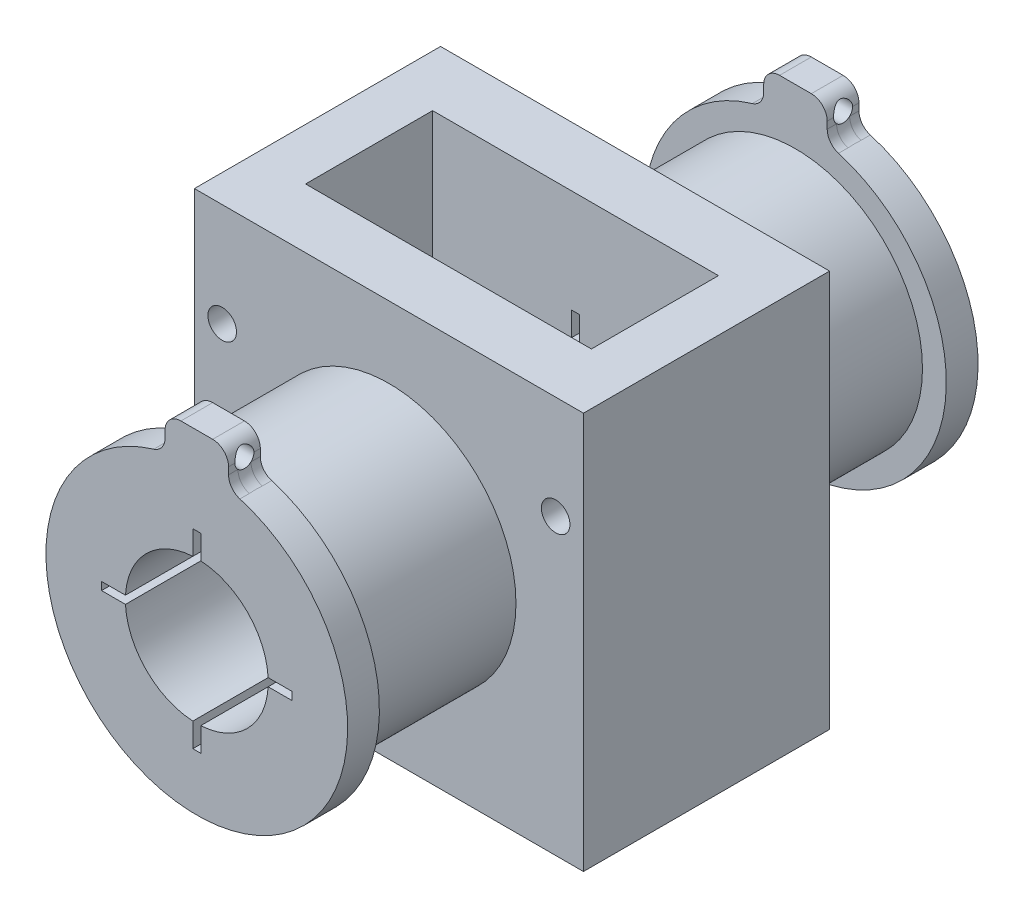
SolidWorks part; units mm, degrees
ref_plane "Front Plane" through (0, 0, 0) normal (0, 0, 1) x (1, 0, 0)
ref_plane "Top Plane" through (0, 0, 0) normal (0, 1, 0) x (1, 0, 0)
ref_plane "Right Plane" through (0, 0, 0) normal (1, 0, 0) x (0, 0, -1)
sketch "Sketch1" plane through (0, 0, 0) normal (0, 0, 1) x (1, 0, 0)
  line L1 (12.25, -12.5) -> (-12.25, -12.5)
  line L2 (12.25, -12.5) -> (12.25, 12.5)
  line L3 (12.25, 12.5) -> (-12.25, 12.5)
  line L4 (-12.25, -12.5) -> (-12.25, 12.5)
  line L5 (12.25, -12.5) -> (-12.25, 12.5) construction
  line L6 (12.25, 12.5) -> (-12.25, -12.5) construction
  point P0 (0, 0)
  dimension "D1" = 24.5
  dimension "D2" = 25
extrude "Boss-Extrude1" add sketch "Sketch1" along normal mid plane 15.5
ref_plane "Plane1" through (0, 0, 7.75) normal (0, 0, 1) x (1, 0, 0)
sketch "Sketch2" plane through (0, 0, 7.75) normal (0, 0, 1) x (1, 0, 0)
  circle A0 centre (0, 0) radius 8
  dimension "D1" = 16
extrude "Boss-Extrude2" add sketch "Sketch2" along normal blind 12.1
mirror "Mirror1" about plane through (0, 0, 0) normal (0, 0, 1) of "Boss-Extrude2"
ref_plane "Plane2" through (0, 0, 19.85) normal (0, 0, 1) x (1, 0, 0)
sketch "Sketch3" plane through (0, 0, 19.85) normal (0, 0, 1) x (1, 0, 0)
  circle A0 centre (0, 0) radius 4.5
  dimension "D1" = 9
extrude "Cut-Extrude1" cut sketch "Sketch3" against normal blind 65
ref_plane "Plane3" through (0, 12.5, 0) normal (0, 1, 0) x (1, 0, 0)
sketch "Sketch4" plane through (0, 12.5, 0) normal (0, 1, 0) x (1, 0, 0)
  line L1 (9, -4) -> (-9, -4)
  line L2 (9, -4) -> (9, 4)
  line L3 (9, 4) -> (-9, 4)
  line L4 (-9, -4) -> (-9, 4)
  line L5 (9, -4) -> (-9, 4) construction
  line L6 (9, 4) -> (-9, -4) construction
  point P0 (0, 0)
  dimension "D1" = 8
  dimension "D2" = 18
extrude "Cut-Extrude2" cut sketch "Sketch4" against normal blind 26
ref_plane "Plane4" through (0, 0, 0) normal (0, 0, 1) x (1, 0, 0)
ref_plane "Plane7" through (0, 0, 19.85) normal (0, 0, 1) x (1, 0, 0)
sketch "Sketch16" plane through (0, 0, 19.85) normal (0, 0, 1) x (1, 0, 0)
  circle A0 centre (0, 0) radius 9.5
  circle A1 centre (0, 0) radius 4.5
  dimension "D1" = 19
  dimension "D2" = 9
extrude "Boss-Extrude6" add sketch "Sketch16" against normal blind 2
mirror "Mirror3" about plane through (0, 0, 0) normal (0, 0, 1) of "Boss-Extrude6"
sketch "Sketch7" plane through (0, 0, 0) normal (0, 0, 1) x (1, 0, 0)
  line L1 (6, 0.25) -> (-6, 0.25)
  line L2 (6, 0.25) -> (6, -0.25)
  line L3 (6, -0.25) -> (-6, -0.25)
  line L4 (-6, 0.25) -> (-6, -0.25)
  line L5 (6, 0.25) -> (-6, -0.25) construction
  line L6 (6, -0.25) -> (-6, 0.25) construction
  point P0 (0, 0)
  dimension "D1" = 12
  dimension "D2" = 0.5
extrude "Cut-Extrude3" cut sketch "Sketch7" against normal mid plane 92.5
pattern_circular "CirPattern1" count 2 over 90 about axis through (0, 0, 17.85) along (0, 0, 1) of "Cut-Extrude3"
sketch "Sketch17" plane through (0, 0, 19.85) normal (0, 0, 1) x (1, 0, 0)
  circle A0 centre (-10.5, 6) radius 0.9
  dimension "D1" = 1.8
  dimension "D2" = 6
  dimension "D3" = 10.5
extrude "Cut-Extrude5" cut sketch "Sketch17" against normal blind 52
mirror "Mirror2" about plane through (0, 0, 0) normal (1, 0, 0) of "Cut-Extrude5"
sketch "Sketch18" plane through (0, 0, 0) normal (1, 0, 0) x (0, 0, -1)
  line L5 (-17.85, -9.5) -> (-17.85, 9.5) construction
  line L6 (-17.85, 8) -> (-19.85, 8)
  line L7 (-17.85, 8) -> (-17.85, 11.5)
  line L8 (-17.85, 11.5) -> (-19.85, 11.5)
  line L9 (-19.85, 8) -> (-19.85, 11.5)
  line L10 (-19.85, 10.45) -> (-19.85, -10.45) construction
  circle A0 centre (-18.85, 10.5) radius 0.6
  dimension "D3" = 1.2
  dimension "D1" = 8
  dimension "D2" = 3.5
  dimension "D4" = 1
  dimension "D5" = 1
extrude "Boss-Extrude7" add sketch "Sketch18" along normal mid plane 4
mirror "Mirror4" about plane through (0, 0, 0) normal (0, 0, 1) of "Boss-Extrude7"
fillet "Fillet1" radius 1 8 edges at (2, 11.5, 18.85) (-2, 11.5, 18.85) (-2, 9.2871, 18.85) (2, 9.2871, 18.85) (-2, 11.5, -18.85) (-2, 9.2871, -18.85) (2, 11.5, -18.85) (2, 9.2871, -18.85)
ref_plane "Plane8" through (0, 0, 7.75) normal (0, 0, 1) x (1, 0, 0)
sketch "Sketch21" plane through (0, 0, 7.75) normal (0, 0, 1) x (1, 0, 0)
  line L1 (-12.25, 12.5) -> (-9.25, 12.5)
  line L2 (-12.25, 12.5) -> (-12.25, 7.5)
  line L3 (-12.25, 7.5) -> (-9.25, 7.5)
  line L4 (-9.25, 12.5) -> (-9.25, 7.5)
  line L5 (12.25, 12.5) -> (9.25, 12.5)
  line L6 (12.25, 12.5) -> (12.25, 7.5)
  line L7 (12.25, 7.5) -> (9.25, 7.5)
  line L8 (9.25, 12.5) -> (9.25, 7.5)
  dimension "D1" = 5
  dimension "D2" = 5
  dimension "D3" = 3
  dimension "D4" = 3
extrude "Boss-Extrude9" [suppressed] add sketch "Sketch21" along normal blind 2.2
mirror "Mirror5" [suppressed] about plane through (0, 0, 0) normal (0, 0, 1)
